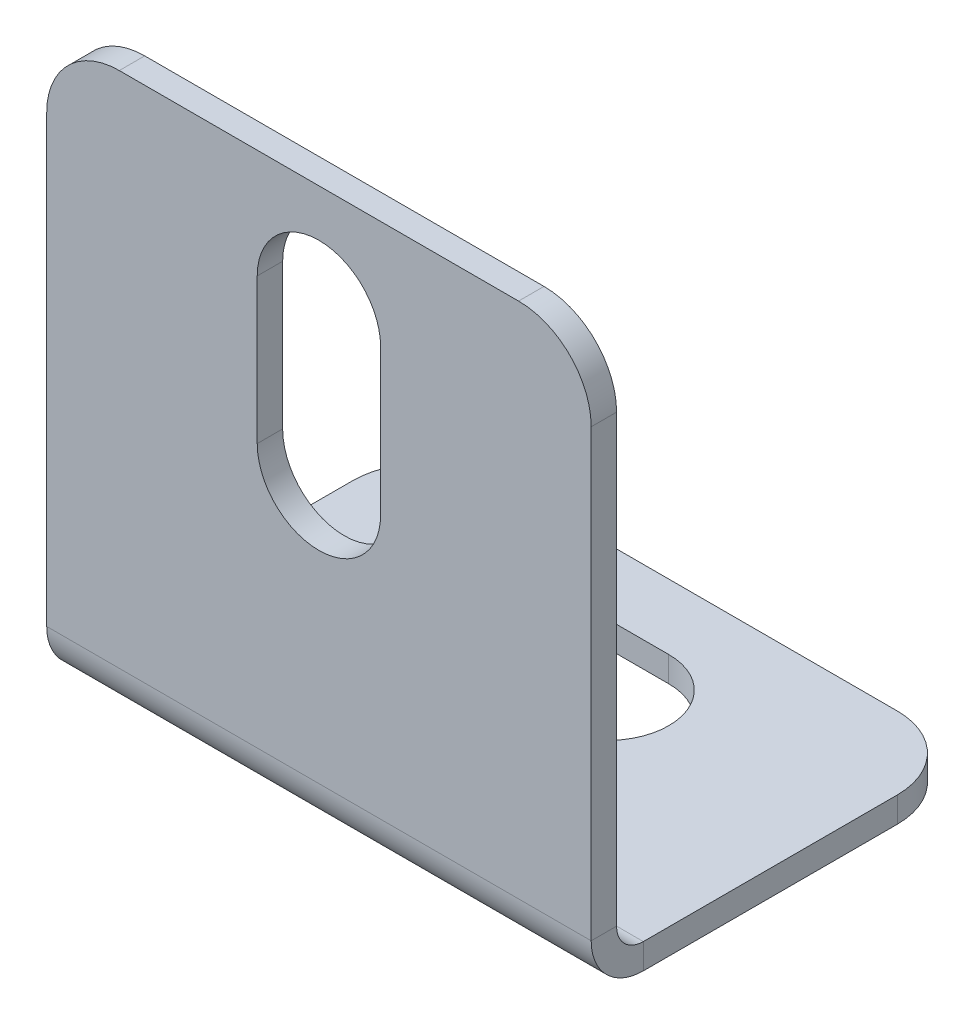
SolidWorks part; units mm, degrees
note: The reader was unsure of these and kept them because the rebuilt part matched: flange length of "Edge-Flange1".
ref_plane "Front Plane" through (0, 0, 0) normal (0, 0, 1) x (1, 0, 0)
ref_plane "Top Plane" through (0, 0, 0) normal (0, 1, 0) x (1, 0, 0)
ref_plane "Right Plane" through (0, 0, 0) normal (1, 0, 0) x (0, 0, -1)
sketch "Sketch1" plane through (0, 0, 0) normal (0, 1, 0) x (1, 0, 0)
  line L1 (0, 0) -> (15, 0)
  line L2 (0, 0) -> (0, -9)
  line L3 (0, -9) -> (15, -9)
  line L4 (15, 0) -> (15, -9)
  dimension "D1" = 15
  dimension "D2" = 9
sheet metal parameters "Sheet-Metal1" thickness 0.7 parameters "D1"=0.7366
base flange "Base-Flange1" sketch "Sketch1" thickness 0.7 reverse thickness direction no parameters "D1"=0.7366
edge flange "Edge-Flange1" sketch "Sketch6" flange angle 90 flange length 15 flange position bend outside bend radius 0.7366 thickness 0.7 relief rectangular parameters "D6"=10
sketch "Sketch6" plane through (0, 0, 9) normal (0, 0, 1) x (1, 0, 0)
  line L0 (0, 0) -> (15, 0) construction
  line L1 (0, 0) -> (15, 0)
  line L2 (0, 0) -> (0, 15)
  line L3 (0, 15) -> (15, 15)
  line L4 (15, 15) -> (15, 0)
bend "EdgeBend1" bend radius 0.7366 bend angle 90 parameters "D5"=1
sketch "Sketch7" plane through (0, 0, 0) normal (0, 1, 0) x (1, 0, 0)
  line L1 (8.5, -3.5) -> (6.5, -3.5) construction
  line L2 (8.5, -5.2) -> (6.5, -5.2)
  line L3 (8.5, -1.8) -> (6.5, -1.8)
  line L4 (15, 0) -> (0, 0) construction
  line L5 (7.5, -9) -> (7.5, 0)
  line L6 (0, -9) -> (15, -9) construction
  arc A0 (8.5, -5.2) -> (8.5, -1.8) centre (8.5, -3.5) ccw
  arc A1 (6.5, -1.8) -> (6.5, -5.2) centre (6.5, -3.5) ccw
  point P2 (7.5, -3.5)
  dimension "D2" = 1.7
  dimension "D1" = 3.5
  dimension "D3" = 2
extrude "Cut-Extrude1" cut sketch "Sketch7" against normal blind 10
fillet "Fillet1" radius 2 4 edges at (0, 15, 10.0866) (15, 15, 10.0866) (0, -0.35, 0) (15, -0.35, 0)
sketch "Sketch8" plane through (0, 0, 9.7366) normal (0, 0, -1) x (-1, 0, 0)
  line L1 (-7.5, 15) -> (-7.5, 0.7366) construction
  line L2 (-13, 15) -> (-2, 15) construction
  line L3 (0, 0.7366) -> (-15, 0.7366) construction
  line L4 (-7.5, 12) -> (-7.5, 8) construction
  line L5 (-5.8, 12) -> (-5.8, 8)
  line L6 (-9.2, 12) -> (-9.2, 8)
  line L7 (0, 0) -> (-15, 0) construction
  arc A0 (-5.8, 12) -> (-9.2, 12) centre (-7.5, 12) ccw
  arc A1 (-9.2, 8) -> (-5.8, 8) centre (-7.5, 8) ccw
  point P2 (-7.5, 10)
  dimension "D1" = 10
  dimension "D3" = 1.7
  dimension "D2" = 4
extrude "Cut-Extrude2" cut sketch "Sketch8" against normal blind 10 normal cut yes
flat pattern "Flat-Pattern1" [suppressed]
sketch "Bend-Lines1" plane through (0, 0, 0) normal (0, 1, 0) x (1, 0, 0)
  line L0 (0, -9.8534) -> (15, -9.8534) construction
  line L1 (0, -9.8534) -> (15, -9.8534) construction
sketch3d "Bounding-Box1" [suppressed]
  line L0 (15, 0, 0) -> (15, -24.9702, 0) construction
  line L1 (0, 0, 0) -> (0, -24.9702, 0) construction
  line L2 (15, 0, 0) -> (0, 0, 0) construction
  line L3 (15, -24.9702, 0) -> (0, -24.9702, 0) construction
bend of the flat pattern "Flatten-<EdgeBend1>1"
